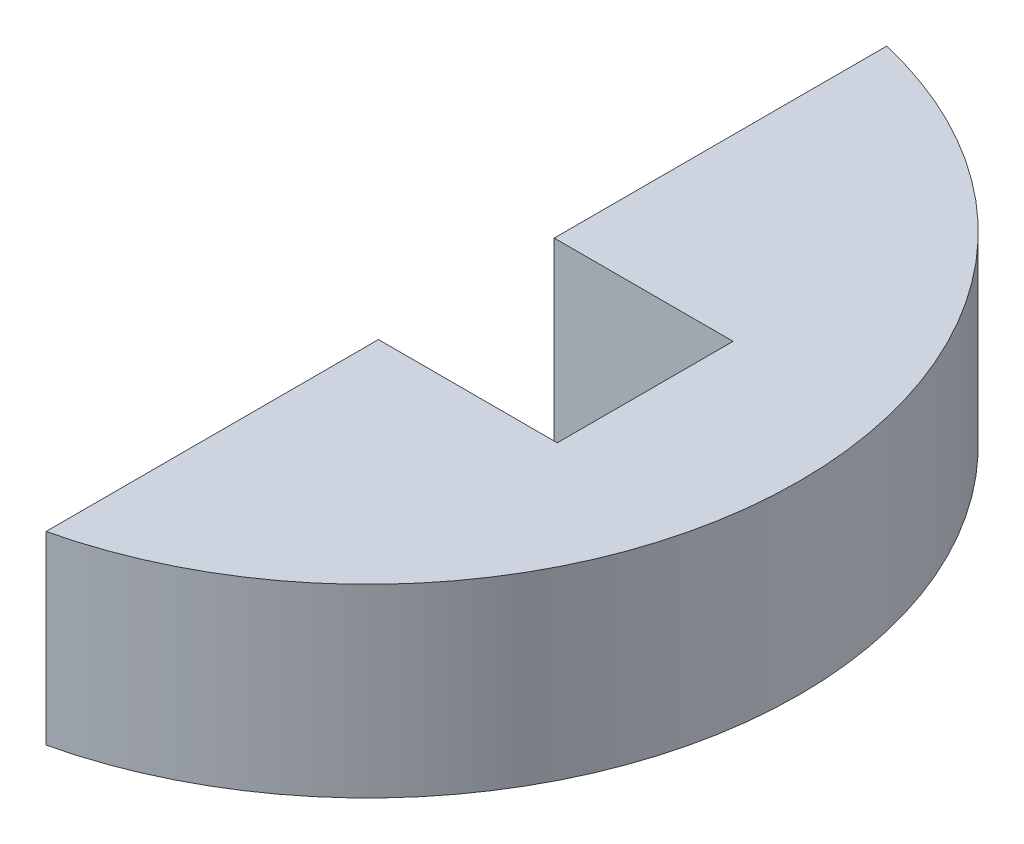
SolidWorks part; units mm, degrees
ref_plane "Front Plane" through (0, 0, 0) normal (0, 0, 1) x (1, 0, 0)
ref_plane "Top Plane" through (0, 0, 0) normal (0, 1, 0) x (1, 0, 0)
ref_plane "Right Plane" through (0, 0, 0) normal (1, 0, 0) x (0, 0, -1)
sketch "Sketch1" plane through (0, 0, 0) normal (0, 1, 0) x (1, 0, 0)
  line L0 (1.6, -6.8147) -> (1.6, -1.425)
  line L1 (1.6, -1.425) -> (4.5, -1.425)
  line L2 (4.5, -1.425) -> (4.5, 1.425)
  line L3 (4.5, 1.425) -> (1.6, 1.425)
  line L4 (1.6, 1.425) -> (1.6, 6.8147)
  line L6 (-1.6, 0) -> (1.6, 0) construction
  line L7 (-1.6, 0) -> (1.6, 0) construction
  line L8 (-7, 0) -> (7, 0) construction
  line L9 (-7, 0) -> (7, 0) construction
  line L10 (0, -7) -> (0, 7) construction
  arc A0 (1.6, -6.8147) -> (1.6, 6.8147) centre (0, 0) ccw
  point P7 (4.5, 0)
  point P8 (0, 0)
  dimension "D1" = 2.85
extrude "Boss-Extrude1" add sketch "Sketch1" along normal blind 1.5 and the other way blind 1.5
